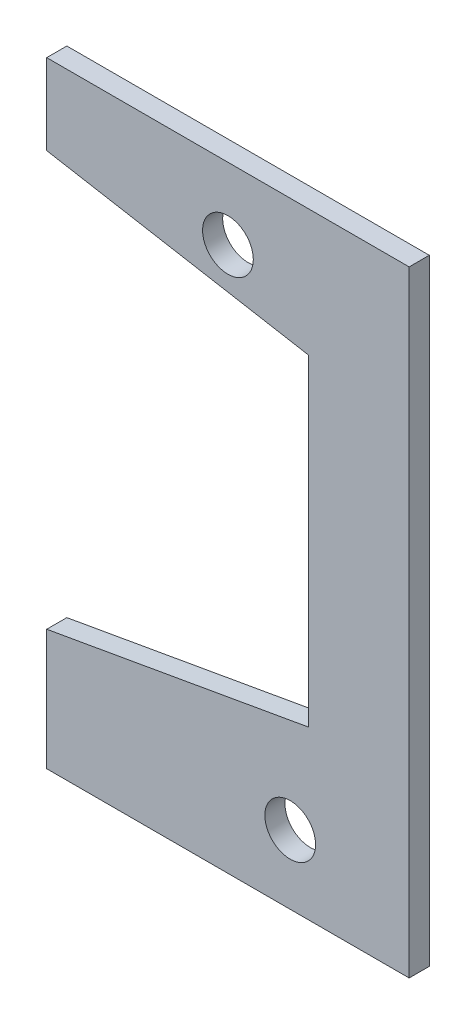
SolidWorks part; units mm, degrees
material "Balsa"
ref_plane "Plan de face" through (0, 0, 0) normal (0, 0, 1) x (1, 0, 0)
ref_plane "Plan de dessus" through (0, 0, 0) normal (0, 1, 0) x (1, 0, 0)
ref_plane "Plan de droite" through (0, 0, 0) normal (1, 0, 0) x (0, 0, -1)
sketch "Esquisse1" plane through (0, 0, 0) normal (0, 0, 1) x (1, 0, 0)
  line L0 (-65, 51.4613) -> (0, 40)
  line L1 (0, 40) -> (0, -40)
  line L2 (-65, -51.4613) -> (0, -40)
  line L4 (-65, -51.4613) -> (-65, -81.4613)
  line L5 (-65, -81.4613) -> (25, -81.4613)
  line L6 (25, -81.4613) -> (25, 71.4613)
  line L7 (25, 71.4613) -> (-65, 71.4613)
  line L8 (-65, 71.4613) -> (-65, 51.4613)
  circle A0 centre (-20, 53.6808) radius 6.3
  circle A1 centre (-4.5339, -64.381) radius 6.3
  dimension "D1" = 12.6
  dimension "D2" = 10
  dimension "D3" = 20
  dimension "D4" = 80
  dimension "D5" = 65
  dimension "D6" = 100
  dimension "D7" = 100
  dimension "D8" = 20
  dimension "D9" = 30
  dimension "D10" = 90
extrude "Boss.-Extru.1" add sketch "Esquisse1" along normal blind 5
